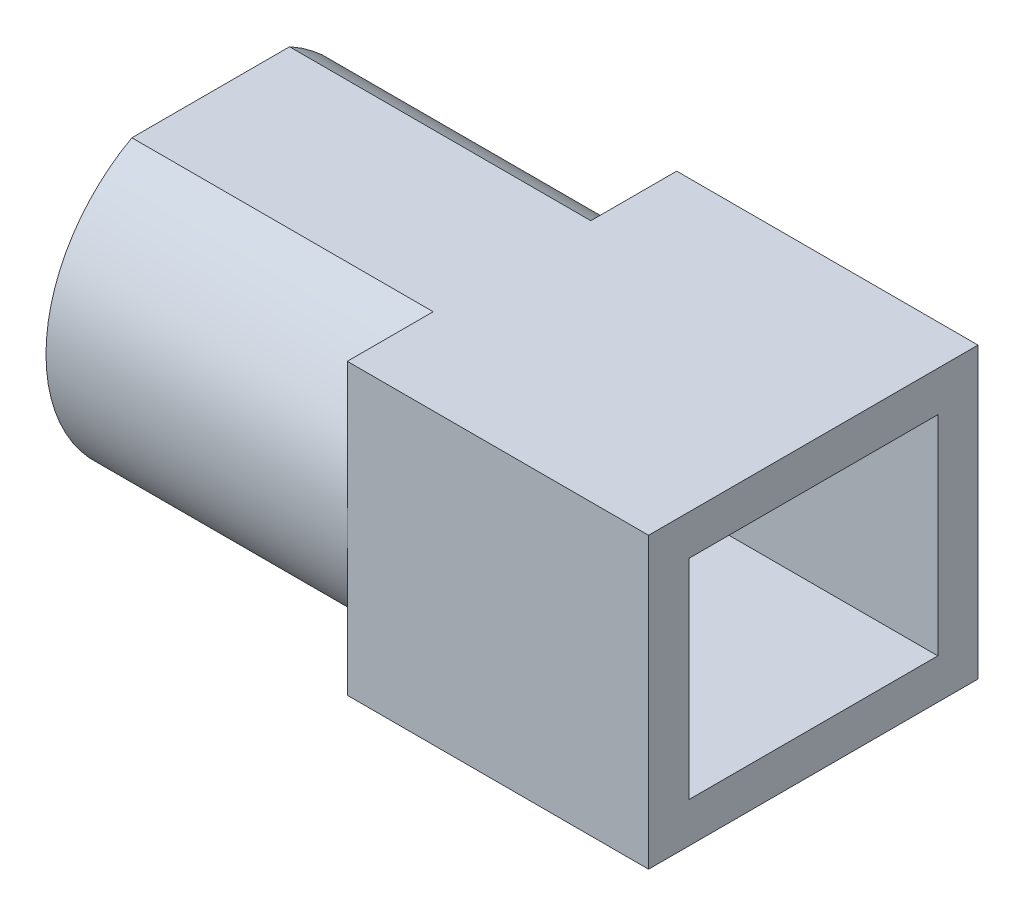
SolidWorks part; units mm, degrees
ref_plane "Front Plane" through (0, 0, 0) normal (0, 0, 1) x (1, 0, 0)
ref_plane "Top Plane" through (0, 0, 0) normal (0, 1, 0) x (1, 0, 0)
ref_plane "Right Plane" through (0, 0, 0) normal (1, 0, 0) x (0, 0, -1)
ref_axis "X" through (-88.99, 0, 0) along (1, 0, 0)
ref_axis "Y" through (0, 55, 0) along (0, -1, 0)
ref_axis "Z" through (0, 0, -88.99) along (0, 0, 1)
sketch "Sketch1" plane through (0, 0, 0) normal (1, 0, 0) x (0, 0, -1)
  line L0 (-8.2, 7.2) -> (-8.2, -7.2)
  line L1 (-6.2, 5.2) -> (6.2, 5.2)
  line L2 (-6.2, 5.2) -> (-6.2, -5.2)
  line L3 (-6.2, -5.2) -> (6.2, -5.2)
  line L4 (6.2, 5.2) -> (6.2, -5.2)
  line L5 (-6.2, 5.2) -> (6.2, -5.2) construction
  line L6 (-6.2, -5.2) -> (6.2, 5.2) construction
  line L7 (-8.2, -7.2) -> (8.2, -7.2)
  line L8 (8.2, 7.2) -> (8.2, -7.2)
  line L9 (-8.2, 7.2) -> (8.2, 7.2)
  point P0 (0, 0)
  dimension "D1" = 10.4
  dimension "D2" = 12.4
  dimension "D3" = 2
ref_plane "Plane1" through (30, 0, 0) normal (1, 0, 0) x (0, 0, -1)
extrude "Boss-Extrude1" add sketch "Sketch1" along normal blind 15 from surface starting at plane "Plane1"
sketch "Sketch2" plane through (0, 0, 0) normal (1, 0, 0) x (0, 0, -1)
  line L0 (-3.9243, 7.2) -> (3.9243, 7.2)
  line L1 (-3.3764, 5.2) -> (3.3764, 5.2)
  line L2 (-3.3764, 5.2) -> (-3.3764, -5.2) construction
  line L3 (-3.3764, -5.2) -> (3.3764, -5.2)
  line L4 (3.3764, 5.2) -> (3.3764, -5.2) construction
  line L5 (-3.3764, 5.2) -> (3.3764, -5.2) construction
  line L6 (-3.3764, -5.2) -> (3.3764, 5.2) construction
  line L7 (-3.9243, -7.2) -> (3.9243, -7.2)
  arc A0 (-3.3764, 5.2) -> (-3.3764, -5.2) centre (0, 0) ccw
  arc A1 (3.3764, -5.2) -> (3.3764, 5.2) centre (0, 0) ccw
  arc A2 (3.9243, -7.2) -> (3.9243, 7.2) centre (0, 0) ccw
  arc A3 (-3.9243, 7.2) -> (-3.9243, -7.2) centre (0, 0) ccw
  point P0 (0, 0)
  point P8 (-4.9469, 3.8246)
  point P9 (-5.3146, -2.7848)
  dimension "D1" = 12.4
  dimension "D2" = 10.4
  dimension "D3" = 2
extrude "Boss-Extrude2" add sketch "Sketch2" against normal blind 15 from surface starting at plane "Plane1"
